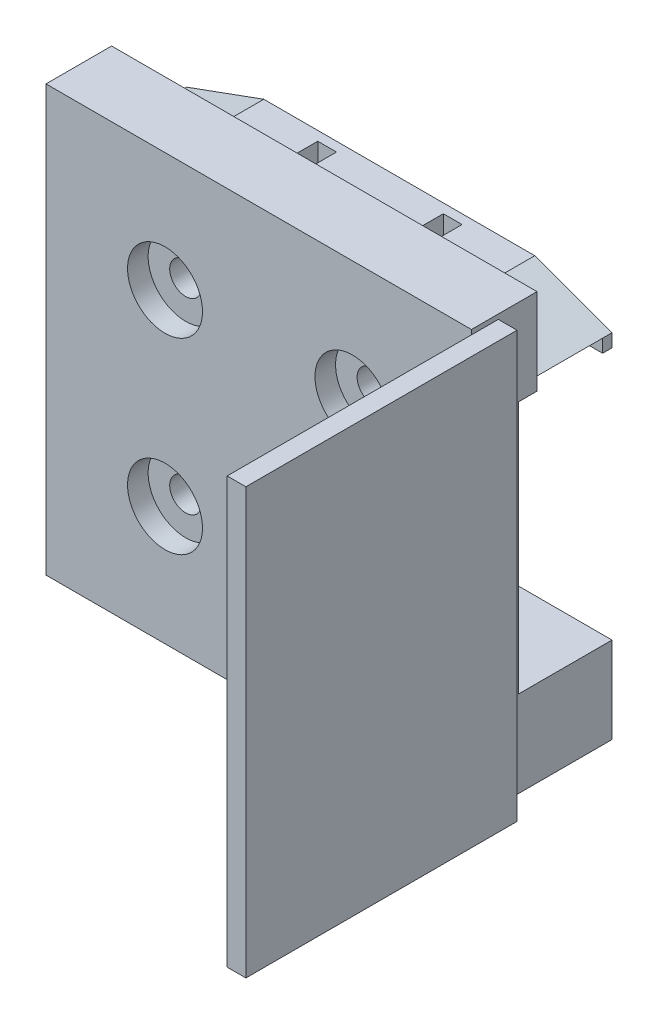
SolidWorks part; units mm, degrees
ref_plane "Front Plane" through (0, 0, 0) normal (0, 0, 1) x (1, 0, 0)
ref_plane "Top Plane" through (0, 0, 0) normal (0, 1, 0) x (1, 0, 0)
ref_plane "Right Plane" through (0, 0, 0) normal (1, 0, 0) x (0, 0, -1)
sketch "Sketch1" plane through (0, 0, 0) normal (0, 0, 1) x (1, 0, 0)
  line L1 (0, 0) -> (45.4, 0)
  line L2 (0, 0) -> (0, 45.4)
  line L3 (0, 45.4) -> (45.4, 45.4)
  line L4 (45.4, 0) -> (45.4, 45.4)
  dimension "D1" = 45.4
  dimension "D2" = 45.4
extrude "Boss-Extrude1" add sketch "Sketch1" along normal blind 15
ref_plane "Plane1" through (0, 0, 12) normal (0, 0, 1) x (1, 0, 0)
sketch "Sketch2" plane through (0, 0, 0) normal (0, 0, -1) x (-1, 0, 0)
  line L0 (-45.4, 0) -> (-45.4, 45.4) construction
  line L1 (-45.4, 36.2) -> (0, 36.2)
  line L2 (-45.4, 36.2) -> (-45.4, 9.2)
  line L3 (-45.4, 9.2) -> (0, 9.2)
  line L4 (0, 36.2) -> (0, 9.2)
  line L5 (0, 45.4) -> (0, 0) construction
  line L6 (-45.4, 22.7) -> (0, 22.7) construction
  point P13 (-45.4, 22.7)
  dimension "D1" = 27
extrude "Cut-Extrude1" cut sketch "Sketch2" against normal blind 10
sketch "Sketch13" plane through (0, 0, 15) normal (0, 0, 1) x (1, 0, 0)
  line L0 (22.7, 45.4) -> (22.7, 0) construction
  line L1 (32.7, 12.7) -> (12.7, 12.7) construction
  line L2 (32.7, 12.7) -> (32.7, 32.7) construction
  line L3 (32.7, 32.7) -> (12.7, 32.7) construction
  line L4 (12.7, 12.7) -> (12.7, 32.7) construction
  line L5 (32.7, 12.7) -> (12.7, 32.7) construction
  line L6 (32.7, 32.7) -> (12.7, 12.7) construction
  line L7 (45.4, 45.4) -> (0, 45.4) construction
  line L8 (0, 0) -> (45.4, 0) construction
  line L9 (0, 22.7) -> (45.4, 22.7) construction
  line L10 (0, 9.2) -> (0, 36.2) construction
  line L11 (45.4, 36.2) -> (45.4, 9.2) construction
  circle A4 centre (32.7, 32.7) radius 1.7
  circle A5 centre (12.7, 32.7) radius 1.7
  circle A6 centre (32.7, 12.7) radius 1.7
  circle A7 centre (12.7, 12.7) radius 1.7
  point P12 (22.7, 22.7)
  point P31 (22.7, 22.7)
  dimension "D1" = 3.4
  dimension "D2" = 20
  dimension "D3" = 20
extrude "Cut-Extrude4" cut sketch "Sketch13" against normal up to next
sketch "Sketch17" plane through (0, 0, 15) normal (0, 0, 1) x (1, 0, 0)
  line L0 (45.4, 22.7) -> (0, 22.7) construction
  line L1 (12.7, 12.7) -> (32.7, 12.7) construction
  line L2 (12.7, 12.7) -> (12.7, 32.7) construction
  line L3 (12.7, 32.7) -> (32.7, 32.7) construction
  line L4 (32.7, 12.7) -> (32.7, 32.7) construction
  line L5 (12.7, 12.7) -> (32.7, 32.7) construction
  line L6 (12.7, 32.7) -> (32.7, 12.7) construction
  line L7 (45.4, 0) -> (45.4, 45.4) construction
  line L8 (0, 45.4) -> (0, 0) construction
  line L9 (22.7, 45.4) -> (22.7, 0) construction
  line L10 (45.4, 45.4) -> (0, 45.4) construction
  line L11 (0, 0) -> (45.4, 0) construction
  circle A0 centre (12.7, 32.7) radius 4
  circle A4 centre (32.7, 32.7) radius 4
  circle A5 centre (32.7, 12.7) radius 4
  circle A6 centre (12.7, 12.7) radius 4
  point P12 (22.7, 22.7)
  point P30 (22.7, 22.7)
  dimension "D1" = 8
  dimension "D2" = 20
  dimension "D3" = 20
extrude "Cut-Extrude8" cut sketch "Sketch17" against normal blind 2.2
sketch "Sketch20" plane through (45.4, 0, 0) normal (1, 0, 0) x (0, 0, -1)
  line L1 (-8, 36.2) -> (-1, 36.2)
  line L2 (-8, 36.2) -> (-8, 37.6)
  line L3 (-8, 37.6) -> (-1, 37.6)
  line L4 (-1, 36.2) -> (-1, 37.6)
  line L5 (-10, 36.2) -> (0, 36.2) construction
  line L6 (0, 36.2) -> (0, 45.4) construction
  dimension "D1" = 1.4
  dimension "D2" = 1
  dimension "D3" = 7
extrude "Cut-Extrude10" cut sketch "Sketch20" against normal blind 15
sketch "Sketch21" plane through (45.4, 0, 0) normal (1, 0, 0) x (0, 0, -1)
  line L0 (-1, 37.6) -> (-8, 37.6) construction
  line L1 (0, 45.4) -> (-8, 45.4)
  line L2 (0, 45.4) -> (0, 40.6)
  line L3 (0, 40.6) -> (-8, 40.6)
  line L4 (-8, 45.4) -> (-8, 40.6)
  dimension "D1" = 8
  dimension "D2" = 3
extrude "Cut-Extrude11" cut sketch "Sketch21" against normal through all
sketch "Sketch22" plane through (0, 0, 0) normal (-1, 0, 0) x (0, 0, 1)
  line L0 (10, 36.2) -> (0, 36.2) construction
  line L1 (1, 36.2) -> (8, 36.2)
  line L2 (1, 36.2) -> (1, 37.6)
  line L3 (1, 37.6) -> (8, 37.6)
  line L4 (8, 36.2) -> (8, 37.6)
  line L5 (0, 40.6) -> (0, 36.2) construction
  dimension "D1" = 7
  dimension "D2" = 1
  dimension "D3" = 1.4
extrude "Cut-Extrude12" cut sketch "Sketch22" against normal blind 15
sketch "Sketch23" plane through (0, 40.6, 0) normal (0, 1, 0) x (1, 0, 0)
  line L0 (0, 0) -> (45.4, 0) construction
  line L1 (30.4, -1) -> (28.4, -1)
  line L2 (30.4, -1) -> (30.4, -8)
  line L3 (30.4, -8) -> (28.4, -8)
  line L4 (28.4, -1) -> (28.4, -8)
  line L5 (17, -8) -> (15, -8)
  line L6 (17, -8) -> (17, -1)
  line L7 (17, -1) -> (15, -1)
  line L8 (15, -8) -> (15, -1)
  line L9 (45.4, -8) -> (45.4, 0) construction
  line L10 (0, -8) -> (0, 0) construction
  dimension "D1" = 2
  dimension "D2" = 2
  dimension "D3" = 7
  dimension "D4" = 7
  dimension "D5" = 1
  dimension "D6" = 1
  dimension "D7" = 15
  dimension "D8" = 15
extrude "Cut-Extrude13" cut sketch "Sketch23" along normal blind 15 and the other way blind 15
chamfer "Chamfer1" distance 3 angle 70 1 edges at (45.4, 40.6, 4) first distance on face at (45.4, 29.3143, 6)
chamfer "Chamfer2" distance 3 angle 70 1 edges at (0, 40.6, 4) first distance on face at (0, 29.3143, 6)
ref_plane "Plane2" through (45.9, 0, 0) normal (1, 0, 0) x (0, 0, -1)
sketch "Sketch26" plane through (45.9, 0, 0) normal (1, 0, 0) x (0, 0, -1)
  line L0 (-15, 45.4) -> (-8, 45.4) construction
  line L1 (-12.6336, 45.4) -> (-41.5683, 45.4)
  line L2 (-12.6336, 45.4) -> (-12.6336, 0)
  line L3 (-12.6336, 0) -> (-41.5683, 0)
  line L4 (-41.5683, 45.4) -> (-41.5683, 0)
extrude "Boss-Extrude4" add sketch "Sketch26" along normal blind 2 separate body
